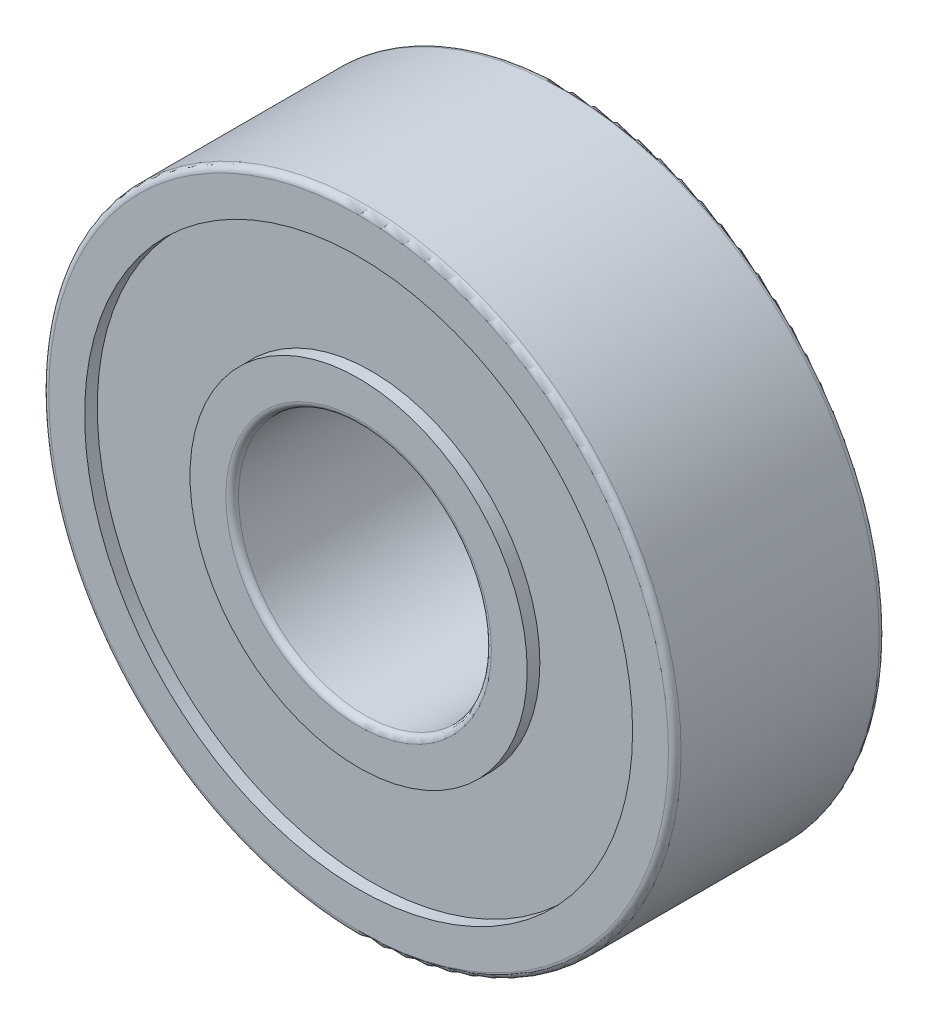
SolidWorks part; units mm, degrees
ref_plane "Front Plane" through (0, 0, 0) normal (0, 0, 1) x (1, 0, 0)
ref_plane "Top Plane" through (0, 0, 0) normal (0, 1, 0) x (1, 0, 0)
ref_plane "Right Plane" through (0, 0, 0) normal (1, 0, 0) x (0, 0, -1)
sketch "Sketch1" plane through (0, 0, 0) normal (0, 0, 1) x (1, 0, 0)
  circle A0 centre (0, 0) radius 3
  circle A1 centre (0, 0) radius 7.5
  dimension "D1" = 6
  dimension "D2" = 15
extrude "Boss-Extrude1" add sketch "Sketch1" along normal blind 5
sketch "Sketch2" plane through (0, 0, 5) normal (0, 0, 1) x (1, 0, 0)
  circle A0 centre (0, 0) radius 7.5 construction
  circle A2 centre (0, 0) radius 3 construction
  circle A3 centre (0, 0) radius 6.5
  circle A6 centre (0, 0) radius 4
  dimension "D1" = 1
  dimension "D2" = 1
extrude "Cut-Extrude1" cut sketch "Sketch2" against normal blind 0.3
extrude "Cut-Extrude2" cut sketch "Sketch2<2>" along normal blind 0.5 from surface starting at face at (7.5, 0, 0)
sketch "Sketch2<2>" plane through (0, 0, 5) normal (0, 0, 1) x (1, 0, 0) same geometry as "Sketch2"
fillet "Fillet1" radius 0.15 4 edges at (3, 0, 5) (7.5, 0, 5) (3, 0, 0) (7.5, 0, 0)
